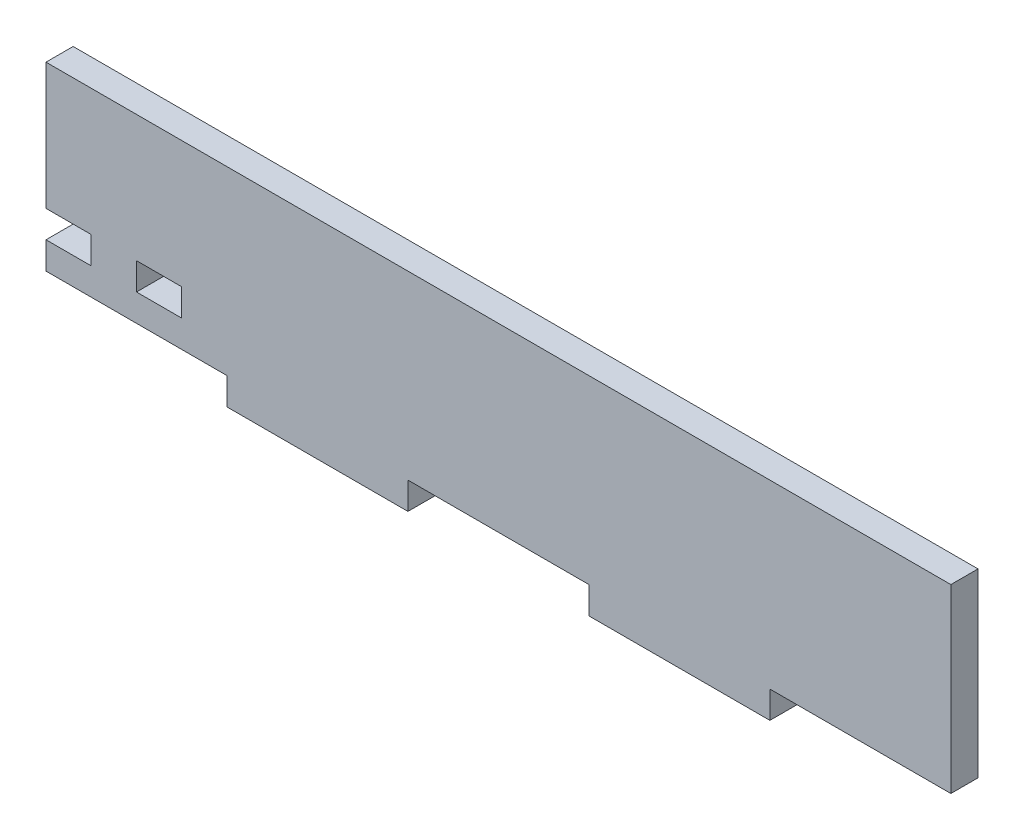
SolidWorks part; units mm, degrees
material "Pine"
ref_plane "Front Plane" through (0, 0, 0) normal (0, 0, 1) x (1, 0, 0)
ref_plane "Top Plane" through (0, 0, 0) normal (0, 1, 0) x (1, 0, 0)
ref_plane "Right Plane" through (0, 0, 0) normal (1, 0, 0) x (0, 0, -1)
sketch "Sketch1" plane through (0, 0, 0) normal (0, 0, 1) x (1, 0, 0)
  line L1 (-100, 23) -> (100, 23)
  line L2 (-100, 23) -> (-100, -23)
  line L3 (-100, -23) -> (100, -23)
  line L4 (100, 23) -> (100, -23)
  line L5 (-100, 23) -> (100, -23) construction
  line L6 (-100, -23) -> (100, 23) construction
  point P0 (0, 0)
  dimension "D1" = 46
  dimension "D2" = 200
extrude "Boss-Extrude1" add sketch "Sketch1" along normal blind 6
sketch "Sketch2" plane through (0, 0, 6) normal (0, 0, 1) x (1, 0, 0)
  line L0 (-20, -23) -> (-20, -17)
  line L1 (-100, -23) -> (-60, -23)
  line L2 (-100, -23) -> (-100, -17)
  line L3 (-100, -17) -> (-60, -17)
  line L4 (-60, -23) -> (-60, -17)
  line L5 (-20, -23) -> (20, -23)
  line L6 (20, -23) -> (20, -17)
  line L7 (-20, -17) -> (20, -17)
  line L8 (60, -23) -> (60, -17)
  line L9 (60, -23) -> (100, -23)
  line L10 (100, -23) -> (100, -17)
  line L11 (60, -17) -> (100, -17)
  dimension "D1" = 40
  dimension "D2" = 6
  dimension "D3" = 3
extrude "Cut-Extrude1" cut sketch "Sketch2" against normal blind 6
sketch "Sketch3" plane through (0, 0, 6) normal (0, 0, 1) x (1, 0, 0)
  line L0 (-100, 23) -> (-100, -17) construction
  line L1 (-100, -11) -> (-90, -11)
  line L2 (-100, -11) -> (-100, -5)
  line L3 (-100, -5) -> (-90, -5)
  line L4 (-90, -11) -> (-90, -5)
  line L5 (-60, -17) -> (-100, -17) construction
  line L6 (-80, -11) -> (-80, -5)
  line L7 (-80, -11) -> (-70, -11)
  line L8 (-70, -11) -> (-70, -5)
  line L9 (-80, -5) -> (-70, -5)
  dimension "D1" = 6
  dimension "D2" = 6
  dimension "D3" = 10
  dimension "D4" = 2
extrude "Cut-Extrude2" cut sketch "Sketch3" against normal blind 10
